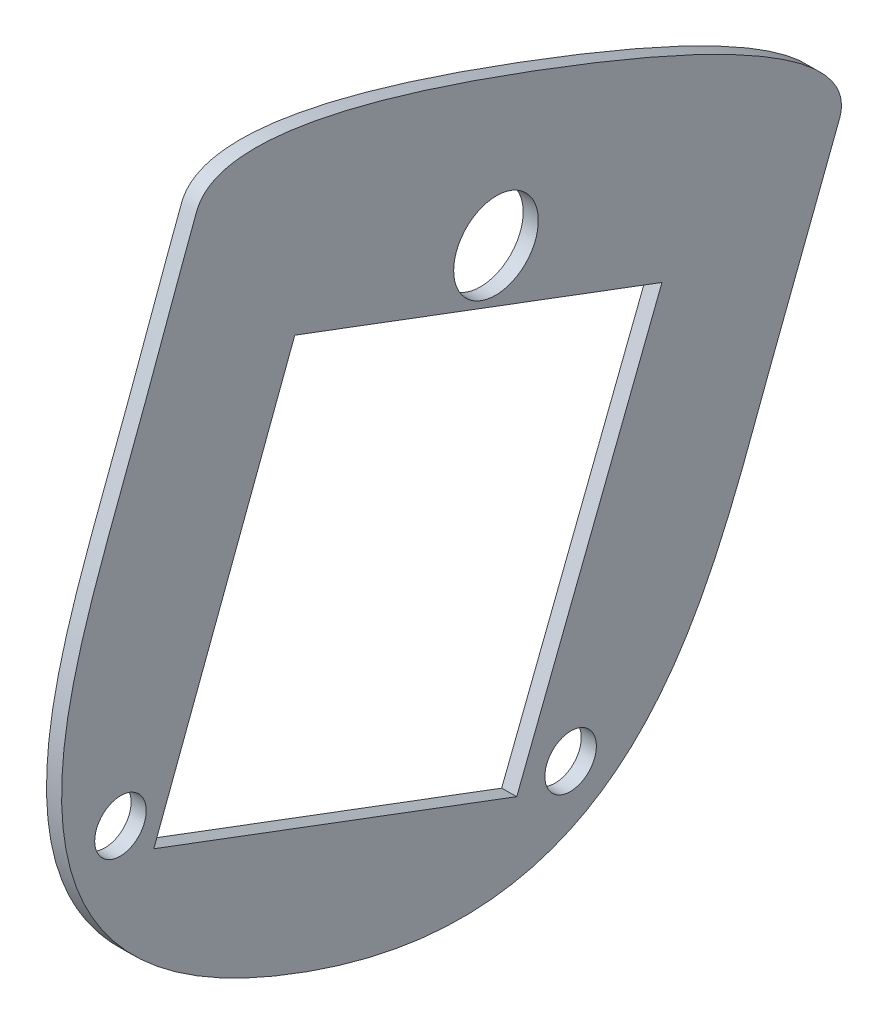
SolidWorks part; units mm, degrees
ref_plane "Front Plane" through (0, 0, 0) normal (0, 0, 1) x (1, 0, 0)
ref_plane "Top Plane" through (0, 0, 0) normal (0, 1, 0) x (1, 0, 0)
ref_plane "Right Plane" through (0, 0, 0) normal (1, 0, 0) x (0, 0, -1)
sketch "Sketch2" plane through (-865.3739, -0.0001, 10.9842) normal (-0.9999, 0, 0.0127) x (0.0127, 0, 0.9999)
  circle A0 centre (-17.1866, -9.2159) radius 6 construction
  circle A1 centre (105.1276, 37.6907) radius 6 construction
  circle A2 centre (-17.1866, -9.2159) radius 6
  circle A3 centre (105.1276, 37.6907) radius 6
  circle A4 centre (2.5155, 122.3361) radius 11.5 construction
  circle A5 centre (2.5155, 122.3361) radius 11.5
  point P0 (86.5551, 152.6282)
  point P1 (81.9504, 150.6796)
  dimension "D4" = 23
  dimension "D1" = 5
ref_plane "Plane1" through (-1179.5486, -0.0001, 14.972) normal (-0.9999, 0, 0.0127) x (0.0127, 0, 0.9999)
sketch "Sketch3" plane through (-1179.5486, -0.0001, 14.972) normal (-0.9999, 0, 0.0127) x (0.0127, 0, 0.9999)
  line L0 (96.0716, 27.7917) -> (57.7586, 127.6973) construction
  line L1 (96.0716, 27.7917) -> (57.7586, 127.6973)
  line L3 (-42.0091, 89.4371) -> (-2.5501, -10.0289)
  line L4 (-42.0091, 89.4371) -> (57.7586, 127.6973)
  line L5 (96.0716, 27.7917) -> (-2.5501, -10.0289)
  circle A3 centre (105.1276, 37.6907) radius 7
  circle A8 centre (3.0884, 120.8422) radius 11.5
  circle A9 centre (-17.1866, -9.2159) radius 7
  spline S0 degree 3 poles (84.5877, 169.5548) (84.1591, 170.6141) (83.6114, 171.6458) (82.4825, 172.9682) (81.1275, 174.0328) (79.6255, 174.8519) (78.0481, 175.4677) (75.8837, 176.0674) (73.1375, 176.4938) (69.8483, 176.6685) (66.5932, 176.6095) (63.379, 176.3823) (60.2073, 176.0282) (57.0754, 175.5759) (53.9806, 175.0444) (50.9193, 174.4483) (47.8886, 173.7975) (44.8855, 173.1008) (40.9147, 172.1178) (36.0066, 170.8019) (30.1862, 169.1128) (24.4167, 167.3312) (18.6809, 165.471) (12.9629, 163.5374) (7.2468, 161.5366) (-0.3928, 158.7797) (-6.166, 156.6131) (-13.9483, 153.6286) (-19.6897, 151.3795) (-27.2134, 148.3214) (-32.8014, 145.9872) (-38.3459, 143.6017) (-43.8547, 141.1498) (-49.3359, 138.6168) (-54.7932, 135.9811) (-59.3225, 133.6777) (-62.9324, 131.7536) (-65.6313, 130.2638) (-68.3201, 128.7213) (-70.995, 127.1176) (-73.6517, 125.4434) (-76.283, 123.6856) (-78.8782, 121.8282) (-81.4203, 119.8479) (-83.8804, 117.7153) (-86.2094, 115.386) (-87.9665, 113.2326) (-89.1751, 111.3395) (-89.9363, 109.8267) (-90.5056, 108.2133) (-90.8014, 106.5155) (-90.7567, 104.7772) (-90.474, 103.6437) (-90.0844, 102.5695) (-89.841, 101.912) (-89.5415, 101.1241) (-89.3902, 100.7305) (-89.238, 100.337) (-89.086, 99.9434) (-88.9335, 99.5497) (-88.7301, 99.0246) (-88.3735, 98.1053) (-87.8622, 96.7909) (-87.2459, 95.2119) (-86.6271, 93.6311) (-86.006, 92.0484) (-85.3828, 90.4637) (-84.7576, 88.8772) (-84.1306, 87.2885) (-83.5021, 85.6979) (-82.662, 83.5742) (-81.6087, 80.9142) (-80.341, 77.7134) (-79.0707, 74.5033) (-77.7994, 71.2836) (-76.5287, 68.0539) (-75.2594, 64.814) (-73.9927, 61.5637) (-72.7309, 58.3024) (-71.4763, 55.0294) (-69.81, 50.6514) (-67.733, 45.1559) (-65.1929, 38.5485) (-63.0021, 33.047) (-61.1797, 28.6615) (-60.0063, 25.9297) (-59.0438, 23.7513) (-58.3093, 22.1218) (-57.5611, 20.497) (-56.7986, 18.8776) (-56.0207, 17.2642) (-55.227, 15.6574) (-54.4159, 14.0579) (-52.7551, 10.8759) (-50.1136, 6.1705) (-46.2141, 0.1062) (-41.8798, -5.6826) (-37.071, -11.0955) (-31.7493, -16.031) (-26.8927, -19.6435) (-22.7717, -22.1827) (-18.509, -24.4734) (-12.9357, -26.8488) (-5.9687, -28.8976) (1.1735, -30.1678) (8.3946, -30.7243) (15.6292, -30.6392) (22.8222, -29.9927) (29.9449, -28.8562) (36.9714, -27.3105) (46.201, -24.7823) (52.9582, -22.4509) (61.8197, -19.0525) (68.4041, -16.2675) (76.9584, -11.9755) (83.2171, -8.426) (89.2737, -4.508) (95.0546, -0.1787) (100.4909, 4.596) (105.488, 9.8386) (109.9491, 15.5591) (113.7592, 21.7413) (116.3146, 27.2342) (117.9522, 31.7877) (119.3182, 36.4313) (120.5136, 42.3647) (121.1702, 49.5927) (121.1263, 56.8326) (120.4783, 64.0347) (119.3229, 71.151) (118.1408, 76.4157) (117.2481, 79.8921) (116.7817, 81.6236) (116.2975, 83.349) (115.7971, 85.0687) (115.2813, 86.7826) (114.7512, 88.4909) (114.2078, 90.1937) (113.467, 92.4568) (112.5129, 95.2725) (110.9356, 99.7518) (108.8862, 105.3072) (106.3571, 111.9184) (104.227, 117.3933) (102.5388, 121.7627) (101.2832, 125.0351) (100.0408, 128.3038) (98.8095, 131.5676) (97.5869, 134.8253) (96.3723, 138.0765) (95.1647, 141.3206) (93.9629, 144.5568) (92.7653, 147.7846) (91.7699, 150.4668) (90.9746, 152.6077) (90.3784, 154.2108) (89.7824, 155.8113) (89.1863, 157.4091) (88.5902, 159.0041) (87.9938, 160.5963) (87.3968, 162.1856) (86.7993, 163.7719) (86.3006, 165.0911) (85.9511, 166.0132) (85.7512, 166.5397) (85.6013, 166.9344) (85.4511, 167.3288) (85.3012, 167.7231) (85.1505, 168.117) (84.8464, 168.9032) (84.5877, 169.5548) (84.1591, 170.6141) (83.6114, 171.6458) knots -0.00321 -0.002568 0 0 0.002678 0.005356 0.008033 0.010711 0.013389 0.016067 0.021422 0.026778 0.032133 0.037489 0.042844 0.0482 0.053555 0.058911 0.064266 0.069622 0.074977 0.085688 0.096399 0.10711 0.117821 0.128532 0.139243 0.149955 0.171377 0.171377 0.192798 0.203509 0.21422 0.224931 0.235641 0.246352 0.257063 0.267774 0.273129 0.278485 0.28384 0.289196 0.294551 0.299906 0.305262 0.310617 0.315973 0.321328 0.326683 0.329361 0.332039 0.334717 0.337394 0.340072 0.34275 0.34275 0.345317 0.345958 0.3466 0.347242 0.347884 0.348525 0.349167 0.350451 0.353018 0.355585 0.358152 0.360719 0.363286 0.365853 0.36842 0.370987 0.373554 0.378688 0.383822 0.388956 0.39409 0.399224 0.404358 0.409492 0.414626 0.419761 0.424895 0.435163 0.445431 0.455699 0.460833 0.465967 0.468534 0.471101 0.473668 0.476235 0.478802 0.481369 0.483936 0.486503 0.496771 0.507039 0.517308 0.527576 0.537844 0.548112 0.553246 0.55838 0.568648 0.578916 0.589184 0.599453 0.609721 0.619989 0.630257 0.640525 0.650793 0.671329 0.671329 0.691871 0.702142 0.712413 0.722684 0.732955 0.743226 0.753497 0.763768 0.774039 0.78431 0.789445 0.794581 0.804852 0.815123 0.825394 0.835665 0.845936 0.856207 0.858774 0.861342 0.86391 0.866478 0.869045 0.871613 0.874181 0.876748 0.881884 0.887019 0.89729 0.907561 0.917832 0.922968 0.928103 0.933239 0.938374 0.94351 0.948645 0.953781 0.958916 0.964052 0.969187 0.971755 0.974323 0.97689 0.979458 0.982026 0.984594 0.987161 0.989729 0.992297 0.993581 0.994223 0.994865 0.995506 0.996148 0.99679 0.997432 1 1 1.002678 1.005356 1.008033 only from (84.3779, 170.0733) to (84.3779, 170.0733)
  spline S1 degree 3 poles (84.5877, 169.5548) (84.1591, 170.6141) (83.6114, 171.6458) (82.4825, 172.9682) (81.1275, 174.0328) (79.6255, 174.8519) (78.0481, 175.4677) (75.8837, 176.0674) (73.1375, 176.4938) (69.8483, 176.6685) (66.5932, 176.6095) (63.379, 176.3823) (60.2073, 176.0282) (57.0754, 175.5759) (53.9806, 175.0444) (50.9193, 174.4483) (47.8886, 173.7975) (44.8855, 173.1008) (40.9147, 172.1178) (36.0066, 170.8019) (30.1862, 169.1128) (24.4167, 167.3312) (18.6809, 165.471) (12.9629, 163.5374) (7.2468, 161.5366) (-0.3928, 158.7797) (-6.166, 156.6131) (-13.9483, 153.6286) (-19.6897, 151.3795) (-27.2134, 148.3214) (-32.8014, 145.9872) (-38.3459, 143.6017) (-43.8547, 141.1498) (-49.3359, 138.6168) (-54.7932, 135.9811) (-59.3225, 133.6777) (-62.9324, 131.7536) (-65.6313, 130.2638) (-68.3201, 128.7213) (-70.995, 127.1176) (-73.6517, 125.4434) (-76.283, 123.6856) (-78.8782, 121.8282) (-81.4203, 119.8479) (-83.8804, 117.7153) (-86.2094, 115.386) (-87.9665, 113.2326) (-89.1751, 111.3395) (-89.9363, 109.8267) (-90.5056, 108.2133) (-90.8014, 106.5155) (-90.7567, 104.7772) (-90.474, 103.6437) (-90.0844, 102.5695) (-89.841, 101.912) (-89.5415, 101.1241) (-89.3902, 100.7305) (-89.238, 100.337) (-89.086, 99.9434) (-88.9335, 99.5497) (-88.7301, 99.0246) (-88.3735, 98.1053) (-87.8622, 96.7909) (-87.2459, 95.2119) (-86.6271, 93.6311) (-86.006, 92.0484) (-85.3828, 90.4637) (-84.7576, 88.8772) (-84.1306, 87.2885) (-83.5021, 85.6979) (-82.662, 83.5742) (-81.6087, 80.9142) (-80.341, 77.7134) (-79.0707, 74.5033) (-77.7994, 71.2836) (-76.5287, 68.0539) (-75.2594, 64.814) (-73.9927, 61.5637) (-72.7309, 58.3024) (-71.4763, 55.0294) (-69.81, 50.6514) (-67.733, 45.1559) (-65.1929, 38.5485) (-63.0021, 33.047) (-61.1797, 28.6615) (-60.0063, 25.9297) (-59.0438, 23.7513) (-58.3093, 22.1218) (-57.5611, 20.497) (-56.7986, 18.8776) (-56.0207, 17.2642) (-55.227, 15.6574) (-54.4159, 14.0579) (-52.7551, 10.8759) (-50.1136, 6.1705) (-46.2141, 0.1062) (-41.8798, -5.6826) (-37.071, -11.0955) (-31.7493, -16.031) (-26.8927, -19.6435) (-22.7717, -22.1827) (-18.509, -24.4734) (-12.9357, -26.8488) (-5.9687, -28.8976) (1.1735, -30.1678) (8.3946, -30.7243) (15.6292, -30.6392) (22.8222, -29.9927) (29.9449, -28.8562) (36.9714, -27.3105) (46.201, -24.7823) (52.9582, -22.4509) (61.8197, -19.0525) (68.4041, -16.2675) (76.9584, -11.9755) (83.2171, -8.426) (89.2737, -4.508) (95.0546, -0.1787) (100.4909, 4.596) (105.488, 9.8386) (109.9491, 15.5591) (113.7592, 21.7413) (116.3146, 27.2342) (117.9522, 31.7877) (119.3182, 36.4313) (120.5136, 42.3647) (121.1702, 49.5927) (121.1263, 56.8326) (120.4783, 64.0347) (119.3229, 71.151) (118.1408, 76.4157) (117.2481, 79.8921) (116.7817, 81.6236) (116.2975, 83.349) (115.7971, 85.0687) (115.2813, 86.7826) (114.7512, 88.4909) (114.2078, 90.1937) (113.467, 92.4568) (112.5129, 95.2725) (110.9356, 99.7518) (108.8862, 105.3072) (106.3571, 111.9184) (104.227, 117.3933) (102.5388, 121.7627) (101.2832, 125.0351) (100.0408, 128.3038) (98.8095, 131.5676) (97.5869, 134.8253) (96.3723, 138.0765) (95.1647, 141.3206) (93.9629, 144.5568) (92.7653, 147.7846) (91.7699, 150.4668) (90.9746, 152.6077) (90.3784, 154.2108) (89.7824, 155.8113) (89.1863, 157.4091) (88.5902, 159.0041) (87.9938, 160.5963) (87.3968, 162.1856) (86.7993, 163.7719) (86.3006, 165.0911) (85.9511, 166.0132) (85.7512, 166.5397) (85.6013, 166.9344) (85.4511, 167.3288) (85.3012, 167.7231) (85.1505, 168.117) (84.8464, 168.9032) (84.5877, 169.5548) (84.1591, 170.6141) (83.6114, 171.6458) knots -0.00321 -0.002568 0 0 0.002678 0.005356 0.008033 0.010711 0.013389 0.016067 0.021422 0.026778 0.032133 0.037489 0.042844 0.0482 0.053555 0.058911 0.064266 0.069622 0.074977 0.085688 0.096399 0.10711 0.117821 0.128532 0.139243 0.149955 0.171377 0.171377 0.192798 0.203509 0.21422 0.224931 0.235641 0.246352 0.257063 0.267774 0.273129 0.278485 0.28384 0.289196 0.294551 0.299906 0.305262 0.310617 0.315973 0.321328 0.326683 0.329361 0.332039 0.334717 0.337394 0.340072 0.34275 0.34275 0.345317 0.345958 0.3466 0.347242 0.347884 0.348525 0.349167 0.350451 0.353018 0.355585 0.358152 0.360719 0.363286 0.365853 0.36842 0.370987 0.373554 0.378688 0.383822 0.388956 0.39409 0.399224 0.404358 0.409492 0.414626 0.419761 0.424895 0.435163 0.445431 0.455699 0.460833 0.465967 0.468534 0.471101 0.473668 0.476235 0.478802 0.481369 0.483936 0.486503 0.496771 0.507039 0.517308 0.527576 0.537844 0.548112 0.553246 0.55838 0.568648 0.578916 0.589184 0.599453 0.609721 0.619989 0.630257 0.640525 0.650793 0.671329 0.671329 0.691871 0.702142 0.712413 0.722684 0.732955 0.743226 0.753497 0.763768 0.774039 0.78431 0.789445 0.794581 0.804852 0.815123 0.825394 0.835665 0.845936 0.856207 0.858774 0.861342 0.86391 0.866478 0.869045 0.871613 0.874181 0.876748 0.881884 0.887019 0.89729 0.907561 0.917832 0.922968 0.928103 0.933239 0.938374 0.94351 0.948645 0.953781 0.958916 0.964052 0.969187 0.971755 0.974323 0.97689 0.979458 0.982026 0.984594 0.987161 0.989729 0.992297 0.993581 0.994223 0.994865 0.995506 0.996148 0.99679 0.997432 1 1 1.002678 1.005356 1.008033 only from (84.3779, 170.0733) to (84.3779, 170.0733)
  spline S2 degree 3 poles (79.7703, 168.0973) (79.654, 168.385) (79.5608, 168.567) (79.34, 168.909) (79.2107, 169.0695) (78.782, 169.5156) (78.4531, 169.7564) (77.7463, 170.1738) (77.3742, 170.347) (76.6181, 170.646) (76.2313, 170.7718) (75.4457, 170.9901) (75.0459, 171.0829) (74.2475, 171.2414) (73.8476, 171.3072) (72.6462, 171.473) (71.8432, 171.5429) (69.4298, 171.6691) (67.8151, 171.6433) (64.5792, 171.4656) (62.9671, 171.312) (59.7615, 170.9206) (58.1658, 170.6823) (54.9849, 170.1436) (53.3996, 169.8431) (48.656, 168.8688) (45.5068, 168.1227) (39.2498, 166.5091) (36.1403, 165.6406) (29.9484, 163.8155) (26.8662, 162.8586) (17.65, 159.8886) (11.5458, 157.7754) (-0.6049, 153.3792) (-6.6499, 151.0973) (-18.6886, 146.4029) (-24.6805, 143.9847) (-36.5791, 138.946) (-42.4872, 136.3273) (-51.2341, 132.1553) (-54.1301, 130.7232) (-59.8634, 127.7454) (-62.7011, 126.2002) (-66.8856, 123.7579) (-68.2675, 122.9231) (-70.9987, 121.2004) (-72.3487, 120.3119) (-74.9994, 118.4656) (-76.2997, 117.5087) (-78.8252, 115.4929) (-80.0492, 114.4377) (-81.7749, 112.7382) (-82.3328, 112.1498) (-83.3836, 110.9299) (-83.8771, 110.2969) (-84.5427, 109.2937) (-84.7517, 108.95) (-85.1321, 108.2356) (-85.3048, 107.8624) (-85.5131, 107.2891) (-85.5741, 107.0954) (-85.6734, 106.7005) (-85.7118, 106.4978) (-85.7567, 106.0923) (-85.7631, 105.8894) (-85.7375, 105.4833) (-85.7033, 105.2783) (-85.5978, 104.885) (-85.5239, 104.6959) (-85.3844, 104.3148) (-85.3142, 104.1244) (-85.1021, 103.5537) (-84.9587, 103.174) (-84.5227, 102.0368) (-84.2284, 101.28) (-83.3473, 99.0091) (-82.7572, 97.4963) (-77.4279, 83.8874) (-72.5683, 71.8388) (-66.7371, 56.6822) (-65.5847, 53.6454) (-63.2813, 47.5713) (-62.1268, 44.5353) (-59.771, 38.4819) (-58.5707, 35.464) (-56.7026, 30.9639) (-56.0686, 29.4684) (-54.7723, 26.4884) (-54.1097, 25.0035) (-50.7192, 17.6341) (-47.7589, 11.8968) (-42.5832, 3.7604) (-40.7366, 1.1258) (-37.7313, -2.6759) (-36.6901, -3.9179) (-35.0604, -5.7377) (-34.5059, -6.337) (-33.3724, -7.5201) (-32.7922, -8.1052) (-29.8441, -10.9713) (-27.345, -13.0666) (-23.3611, -15.8788) (-21.9939, -16.761) (-19.1769, -18.4096) (-17.7261, -19.1766) (-10.2663, -22.7) (-3.9825, -24.3776) (3.3729, -25.2321) (4.1924, -25.3124) (5.8269, -25.4445) (6.6433, -25.4963) (9.09, -25.6118) (10.7178, -25.6352) (15.5924, -25.5618) (18.8302, -25.3221) (23.6723, -24.7256) (25.2838, -24.487) (28.5025, -23.9384) (30.1115, -23.628) (34.9193, -22.6026) (38.0868, -21.7953) (44.3622, -19.9846) (47.4703, -18.982) (52.0947, -17.3537) (53.6299, -16.7903) (56.6886, -15.6251) (58.2124, -15.0236) (62.7493, -13.1641) (65.733, -11.8489) (71.6057, -9.0437) (74.4945, -7.5535) (80.1538, -4.3544) (82.9251, -2.6472) (86.9704, 0.1194) (88.3001, 1.0763) (90.263, 2.5701) (90.9119, 3.0777) (92.1913, 4.1078) (92.8227, 4.6309) (95.9368, 7.2882) (98.2906, 9.5479) (101.5765, 13.1758) (102.631, 14.4249) (104.1451, 16.3643) (104.6385, 17.0217) (105.6014, 18.3598) (106.0705, 19.0401) (108.3321, 22.4686) (109.8916, 25.3227) (112.4961, 31.2603) (113.5391, 34.3445) (114.5167, 38.3452) (114.696, 39.1533) (115.0193, 40.7681) (115.1639, 41.5767) (115.5483, 44.0063) (115.7388, 45.6309) (116.1311, 50.5177) (116.1533, 53.7931) (115.9328, 57.9055) (115.8763, 58.7278) (115.7406, 60.3643) (115.6615, 61.1797) (115.3922, 63.6178) (115.1705, 65.2327) (114.3953, 70.0494) (113.7318, 73.2236) (112.1864, 79.5171) (111.3038, 82.6361) (109.3954, 88.8382) (108.3675, 91.9207) (106.215, 98.0612) (105.0894, 101.1202) (102.7905, 107.2203) (101.6164, 110.261) (99.26, 116.3391) (98.0812, 119.3779) (95.7512, 125.4661) (94.5998, 128.5155) (91.1648, 137.6705) (88.9043, 143.7849) (85.4993, 152.9511) (84.362, 156.0057) (82.6444, 160.5831) (82.0699, 162.1082) (81.2041, 164.3942) (80.9151, 165.1561) (80.4796, 166.2982) (80.3329, 166.6783) (80.1095, 167.2472) (79.9971, 167.5314) (79.8836, 167.8152) (79.8078, 168.0043) (79.7703, 168.0973) (79.654, 168.385) (79.5608, 168.567) knots -0.000488 -0.000488 0 0 0.000977 0.000977 0.001953 0.001953 0.003906 0.003906 0.005859 0.005859 0.007812 0.007812 0.009766 0.009766 0.011719 0.011719 0.015625 0.015625 0.023437 0.023437 0.03125 0.03125 0.039062 0.039062 0.046875 0.046875 0.0625 0.0625 0.078125 0.078125 0.09375 0.09375 0.125 0.125 0.15625 0.15625 0.1875 0.1875 0.21875 0.21875 0.234375 0.234375 0.25 0.25 0.257812 0.257812 0.265625 0.265625 0.273437 0.273437 0.28125 0.28125 0.285156 0.285156 0.289062 0.289062 0.291016 0.291016 0.292969 0.292969 0.293945 0.293945 0.294922 0.294922 0.295898 0.295898 0.296875 0.296875 0.297852 0.297852 0.298828 0.298828 0.300781 0.300781 0.304687 0.304687 0.3125 0.3125 0.375 0.375 0.390625 0.390625 0.40625 0.40625 0.421875 0.421875 0.429687 0.429687 0.4375 0.4375 0.46875 0.46875 0.484375 0.484375 0.492187 0.492187 0.496094 0.496094 0.5 0.5 0.515625 0.515625 0.523437 0.523437 0.53125 0.53125 0.5625 0.5625 0.566406 0.566406 0.570312 0.570312 0.578125 0.578125 0.59375 0.59375 0.601562 0.601562 0.609375 0.609375 0.625 0.625 0.640625 0.640625 0.648437 0.648437 0.65625 0.65625 0.671875 0.671875 0.6875 0.6875 0.703125 0.703125 0.710937 0.710937 0.714844 0.714844 0.71875 0.71875 0.734375 0.734375 0.742187 0.742187 0.746094 0.746094 0.75 0.75 0.765625 0.765625 0.78125 0.78125 0.785156 0.785156 0.789062 0.789062 0.796875 0.796875 0.8125 0.8125 0.816406 0.816406 0.820312 0.820312 0.828125 0.828125 0.84375 0.84375 0.859375 0.859375 0.875 0.875 0.890625 0.890625 0.90625 0.90625 0.921875 0.921875 0.9375 0.9375 0.96875 0.96875 0.984375 0.984375 0.992187 0.992187 0.996094 0.996094 0.998047 0.998047 0.999023 0.999512 0.999512 1 1 1.000977 1.000977 1.001953 only from (79.7315, 168.1932) to (79.7315, 168.1932)
  spline S3 degree 3 poles (79.7703, 168.0973) (79.654, 168.385) (79.5608, 168.567) (79.34, 168.909) (79.2107, 169.0695) (78.782, 169.5156) (78.4531, 169.7564) (77.7463, 170.1738) (77.3742, 170.347) (76.6181, 170.646) (76.2313, 170.7718) (75.4457, 170.9901) (75.0459, 171.0829) (74.2475, 171.2414) (73.8476, 171.3072) (72.6462, 171.473) (71.8432, 171.5429) (69.4298, 171.6691) (67.8151, 171.6433) (64.5792, 171.4656) (62.9671, 171.312) (59.7615, 170.9206) (58.1658, 170.6823) (54.9849, 170.1436) (53.3996, 169.8431) (48.656, 168.8688) (45.5068, 168.1227) (39.2498, 166.5091) (36.1403, 165.6406) (29.9484, 163.8155) (26.8662, 162.8586) (17.65, 159.8886) (11.5458, 157.7754) (-0.6049, 153.3792) (-6.6499, 151.0973) (-18.6886, 146.4029) (-24.6805, 143.9847) (-36.5791, 138.946) (-42.4872, 136.3273) (-51.2341, 132.1553) (-54.1301, 130.7232) (-59.8634, 127.7454) (-62.7011, 126.2002) (-66.8856, 123.7579) (-68.2675, 122.9231) (-70.9987, 121.2004) (-72.3487, 120.3119) (-74.9994, 118.4656) (-76.2997, 117.5087) (-78.8252, 115.4929) (-80.0492, 114.4377) (-81.7749, 112.7382) (-82.3328, 112.1498) (-83.3836, 110.9299) (-83.8771, 110.2969) (-84.5427, 109.2937) (-84.7517, 108.95) (-85.1321, 108.2356) (-85.3048, 107.8624) (-85.5131, 107.2891) (-85.5741, 107.0954) (-85.6734, 106.7005) (-85.7118, 106.4978) (-85.7567, 106.0923) (-85.7631, 105.8894) (-85.7375, 105.4833) (-85.7033, 105.2783) (-85.5978, 104.885) (-85.5239, 104.6959) (-85.3844, 104.3148) (-85.3142, 104.1244) (-85.1021, 103.5537) (-84.9587, 103.174) (-84.5227, 102.0368) (-84.2284, 101.28) (-83.3473, 99.0091) (-82.7572, 97.4963) (-77.4279, 83.8874) (-72.5683, 71.8388) (-66.7371, 56.6822) (-65.5847, 53.6454) (-63.2813, 47.5713) (-62.1268, 44.5353) (-59.771, 38.4819) (-58.5707, 35.464) (-56.7026, 30.9639) (-56.0686, 29.4684) (-54.7723, 26.4884) (-54.1097, 25.0035) (-50.7192, 17.6341) (-47.7589, 11.8968) (-42.5832, 3.7604) (-40.7366, 1.1258) (-37.7313, -2.6759) (-36.6901, -3.9179) (-35.0604, -5.7377) (-34.5059, -6.337) (-33.3724, -7.5201) (-32.7922, -8.1052) (-29.8441, -10.9713) (-27.345, -13.0666) (-23.3611, -15.8788) (-21.9939, -16.761) (-19.1769, -18.4096) (-17.7261, -19.1766) (-10.2663, -22.7) (-3.9825, -24.3776) (3.3729, -25.2321) (4.1924, -25.3124) (5.8269, -25.4445) (6.6433, -25.4963) (9.09, -25.6118) (10.7178, -25.6352) (15.5924, -25.5618) (18.8302, -25.3221) (23.6723, -24.7256) (25.2838, -24.487) (28.5025, -23.9384) (30.1115, -23.628) (34.9193, -22.6026) (38.0868, -21.7953) (44.3622, -19.9846) (47.4703, -18.982) (52.0947, -17.3537) (53.6299, -16.7903) (56.6886, -15.6251) (58.2124, -15.0236) (62.7493, -13.1641) (65.733, -11.8489) (71.6057, -9.0437) (74.4945, -7.5535) (80.1538, -4.3544) (82.9251, -2.6472) (86.9704, 0.1194) (88.3001, 1.0763) (90.263, 2.5701) (90.9119, 3.0777) (92.1913, 4.1078) (92.8227, 4.6309) (95.9368, 7.2882) (98.2906, 9.5479) (101.5765, 13.1758) (102.631, 14.4249) (104.1451, 16.3643) (104.6385, 17.0217) (105.6014, 18.3598) (106.0705, 19.0401) (108.3321, 22.4686) (109.8916, 25.3227) (112.4961, 31.2603) (113.5391, 34.3445) (114.5167, 38.3452) (114.696, 39.1533) (115.0193, 40.7681) (115.1639, 41.5767) (115.5483, 44.0063) (115.7388, 45.6309) (116.1311, 50.5177) (116.1533, 53.7931) (115.9328, 57.9055) (115.8763, 58.7278) (115.7406, 60.3643) (115.6615, 61.1797) (115.3922, 63.6178) (115.1705, 65.2327) (114.3953, 70.0494) (113.7318, 73.2236) (112.1864, 79.5171) (111.3038, 82.6361) (109.3954, 88.8382) (108.3675, 91.9207) (106.215, 98.0612) (105.0894, 101.1202) (102.7905, 107.2203) (101.6164, 110.261) (99.26, 116.3391) (98.0812, 119.3779) (95.7512, 125.4661) (94.5998, 128.5155) (91.1648, 137.6705) (88.9043, 143.7849) (85.4993, 152.9511) (84.362, 156.0057) (82.6444, 160.5831) (82.0699, 162.1082) (81.2041, 164.3942) (80.9151, 165.1561) (80.4796, 166.2982) (80.3329, 166.6783) (80.1095, 167.2472) (79.9971, 167.5314) (79.8836, 167.8152) (79.8078, 168.0043) (79.7703, 168.0973) (79.654, 168.385) (79.5608, 168.567) knots -0.000488 -0.000488 0 0 0.000977 0.000977 0.001953 0.001953 0.003906 0.003906 0.005859 0.005859 0.007812 0.007812 0.009766 0.009766 0.011719 0.011719 0.015625 0.015625 0.023437 0.023437 0.03125 0.03125 0.039062 0.039062 0.046875 0.046875 0.0625 0.0625 0.078125 0.078125 0.09375 0.09375 0.125 0.125 0.15625 0.15625 0.1875 0.1875 0.21875 0.21875 0.234375 0.234375 0.25 0.25 0.257812 0.257812 0.265625 0.265625 0.273437 0.273437 0.28125 0.28125 0.285156 0.285156 0.289062 0.289062 0.291016 0.291016 0.292969 0.292969 0.293945 0.293945 0.294922 0.294922 0.295898 0.295898 0.296875 0.296875 0.297852 0.297852 0.298828 0.298828 0.300781 0.300781 0.304687 0.304687 0.3125 0.3125 0.375 0.375 0.390625 0.390625 0.40625 0.40625 0.421875 0.421875 0.429687 0.429687 0.4375 0.4375 0.46875 0.46875 0.484375 0.484375 0.492187 0.492187 0.496094 0.496094 0.5 0.5 0.515625 0.515625 0.523437 0.523437 0.53125 0.53125 0.5625 0.5625 0.566406 0.566406 0.570312 0.570312 0.578125 0.578125 0.59375 0.59375 0.601562 0.601562 0.609375 0.609375 0.625 0.625 0.640625 0.640625 0.648437 0.648437 0.65625 0.65625 0.671875 0.671875 0.6875 0.6875 0.703125 0.703125 0.710937 0.710937 0.714844 0.714844 0.71875 0.71875 0.734375 0.734375 0.742187 0.742187 0.746094 0.746094 0.75 0.75 0.765625 0.765625 0.78125 0.78125 0.785156 0.785156 0.789062 0.789062 0.796875 0.796875 0.8125 0.8125 0.816406 0.816406 0.820312 0.820312 0.828125 0.828125 0.84375 0.84375 0.859375 0.859375 0.875 0.875 0.890625 0.890625 0.90625 0.90625 0.921875 0.921875 0.9375 0.9375 0.96875 0.96875 0.984375 0.984375 0.992187 0.992187 0.996094 0.996094 0.998047 0.998047 0.999023 0.999512 0.999512 1 1 1.000977 1.000977 1.001953 only from (79.7315, 168.1932) to (79.7315, 168.1932)
extrude "Boss-Extrude1" add sketch "Sketch3" against normal blind 4 contours S1 S3 | S3 A8 A9 A3 L1 L5 L3 L4 region at (-1179.9823, -9.6438, -19.1964) region at (-1179.9212, -7.4934, -14.382)
